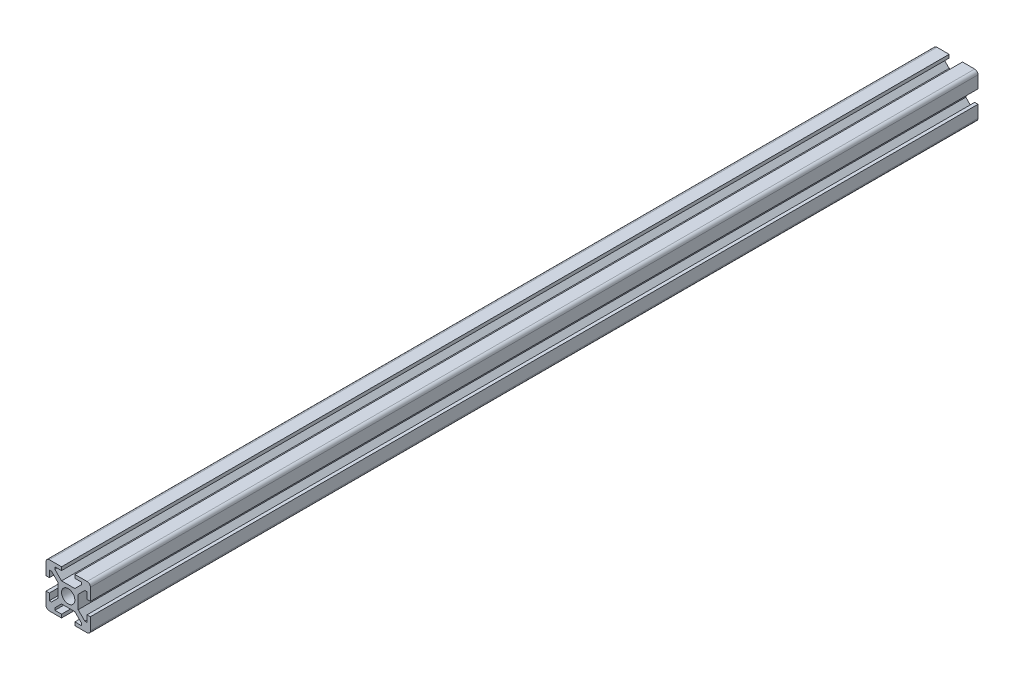
SolidWorks part; units mm, degrees
ref_plane "Plan de face" through (0, 0, 0) normal (0, 0, 1) x (1, 0, 0)
ref_plane "Plan de dessus" through (0, 0, 0) normal (0, 1, 0) x (1, 0, 0)
ref_plane "Plan de droite" through (0, 0, 0) normal (1, 0, 0) x (0, 0, -1)
sketch "Esquisse1" plane through (0, 0, 0) normal (0, 0, 1) x (1, 0, 0)
  line L0 (-10, 10) -> (10, -10) construction
  line L1 (-10, 10) -> (10, 10)
  line L2 (-10, 10) -> (-10, -10)
  line L3 (-10, -10) -> (10, -10)
  line L4 (10, 10) -> (10, -10)
  dimension "D1" = 20
extrude "Extrusion1" add sketch "Esquisse1" along normal mid plane 400
fillet "Congé1" radius 1.5 4 edges at (-10, -10, 0) (10, -10, 0) (-10, 10, 0) (10, 10, 0)
sketch "Esquisse2" plane through (0, 0, -200) normal (0, 0, -1) x (-1, 0, 0)
  line L0 (-10, 3) -> (-10, -3)
  line L1 (-10, -8.5) -> (-10, 8.5) construction
  line L2 (-10, -3) -> (-8.5, -3)
  line L3 (-8.5, -3) -> (-8.5, -6)
  line L4 (-8.5, 6) -> (-7.5, 6)
  line L5 (-4.5, -3) -> (-4.5, 3)
  line L6 (-7.5, 6) -> (-4.5, 3)
  line L7 (-8.5, 6) -> (-8.5, 3)
  line L8 (-8.5, 3) -> (-10, 3)
  line L9 (0, 0) -> (-10, 0) construction
  line L10 (-8.5, -6) -> (-7.5, -6)
  line L11 (-7.5, -6) -> (-4.5, -3)
  point P4 (-10, 0)
  dimension "D1" = 6
  dimension "D2" = 12
  dimension "D3" = 1.5
  dimension "D4" = 5.5
  dimension "D5" = 135
extrude "Enlèv. mat.-Extru.1" cut sketch "Esquisse2" against normal through all
ref_axis "Axe1" through (0, 0, 9.3338) along (0, 0, -1)
pattern_circular "Répétition circulaire1" count 4 over 360 about axis through (0, 0, 9.3338) along (0, 0, -1) of "Enlèv. mat.-Extru.1"
hole_wizard "Trou taraudé M6x1.01" positions "Esquisse4" profile "Esquisse5" tap size "M6x1.0" standard "Ansi Métrique"
sketch "Esquisse4" plane through (0, 0, -200) normal (0, 0, -1) x (-1, 0, 0)
  point P0 (0, 0)
sketch "Esquisse5" plane through (0, 0, -200) normal (1, 0, 0) x (0, 1, 0)
  line L0 (0, 0) -> (0, 31.5022)
  line L1 (0, 31.5022) -> (2.5, 30)
  line L2 (2.5, 30) -> (2.5, 24)
  line L3 (2.5, 24) -> (3, 24)
  line L4 (3, 24) -> (3, 0)
  line L5 (3, 0) -> (0, 0)
  line L10 (0, 31.5022) -> (-2.5, 30) construction
  line L11 (0, -6.35) -> (0, 107.95) construction
  dimension "Diamètre du trou pour taraudage" = 5
  dimension "Profondeur du trou pour taraudage" = 30
  dimension "Diamètre principal du filetage" = 6
  dimension "Profondeur du filetage" = 24
  dimension "Angle de pointe" = 118
mirror "Symétrie1" about plane through (0, 0, 0) normal (0, 0, 1) of "Trou taraudé M6x1.01"
